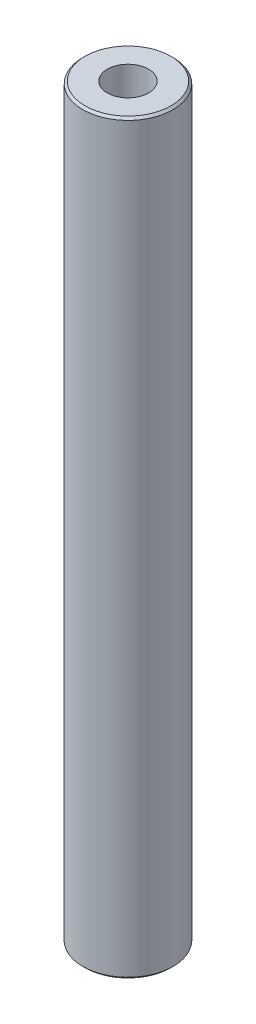
SolidWorks part; units mm, degrees
ref_plane "Front Plane" through (0, 0, 0) normal (0, 0, 1) x (1, 0, 0)
ref_plane "Top Plane" through (0, 0, 0) normal (0, 1, 0) x (1, 0, 0)
ref_plane "Right Plane" through (0, 0, 0) normal (1, 0, 0) x (0, 0, -1)
sketch "Sketch1" plane through (0, 0, 0) normal (0, 1, 0) x (1, 0, 0)
  circle A0 centre (0, 0) radius 15
  dimension "SHAFT_OD" = 30
extrude "Boss-Extrude1" add sketch "Sketch1" along normal blind 248.1337
sketch "Sketch2" plane through (0, 0, 0) normal (0, 1, 0) x (1, 0, 0)
  circle A0 centre (0, 0) radius 6.864
  dimension "BORE_D" = 13.728
extrude "Cut-Extrude1" cut sketch "Sketch2" along normal through all
chamfer "Chamfer1" distance 0.7245 angle 45 2 edges at (0, 248.1337, 15) (0, 0, 15)
